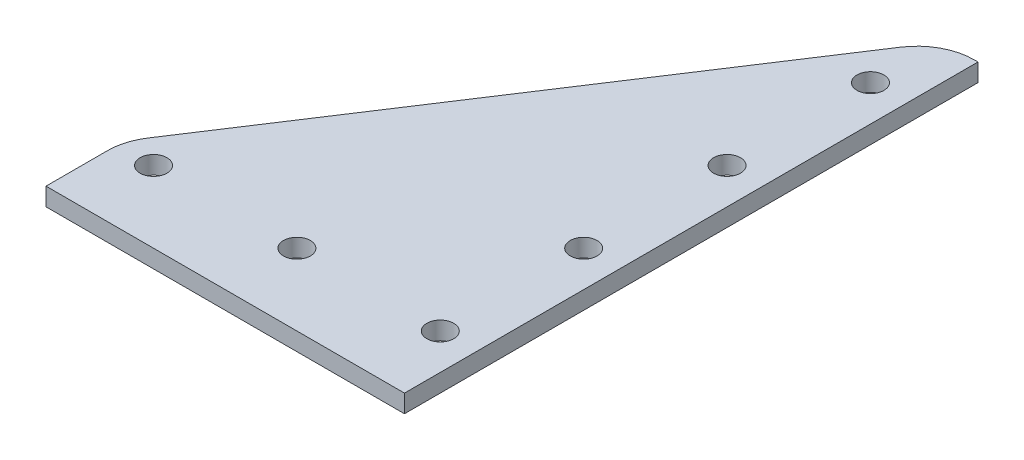
SolidWorks part; units mm, degrees
ref_plane "Front Plane" through (0, 0, 0) normal (0, 0, 1) x (1, 0, 0)
ref_plane "Top Plane" through (0, 0, 0) normal (0, 1, 0) x (1, 0, 0)
ref_plane "Right Plane" through (0, 0, 0) normal (1, 0, 0) x (0, 0, -1)
sketch "Sketch1" plane through (0, 0, 0) normal (0, 1, 0) x (1, 0, 0)
  line L1 (-31.75, 50.8) -> (31.75, 50.8)
  line L2 (-31.75, 50.8) -> (-31.75, -50.8)
  line L3 (-31.75, -50.8) -> (31.75, -50.8)
  line L4 (31.75, 50.8) -> (31.75, -50.8)
  line L5 (-31.75, 50.8) -> (31.75, -50.8) construction
  line L6 (-31.75, -50.8) -> (31.75, 50.8) construction
  point P0 (0, 0)
  dimension "D1" = 101.6
  dimension "D2" = 63.5
extrude "Boss-Extrude1" add sketch "Sketch1" along normal blind 3.175
sketch "Sketch2" plane through (0, 3.175, 0) normal (0, 1, 0) x (1, 0, 0)
  line L0 (-31.75, -50.8) -> (31.75, -50.8) construction
  line L1 (31.75, -50.8) -> (31.75, 50.8) construction
  circle A0 centre (25.4, -38.1) radius 2.3812
  circle A1 centre (25.4, -12.7) radius 2.3812
  circle A2 centre (25.4, 12.7) radius 2.3812
  circle A3 centre (25.4, 38.1) radius 2.3812
  circle A4 centre (0, -38.1) radius 2.3812
  circle A5 centre (-25.4, -38.1) radius 2.3812
  circle A6 centre (-50.8, -38.1) radius 2.3812
  dimension "D1" = 4.7625
  dimension "D2" = 12.7
  dimension "D3" = 6.35
  dimension "D4" = 4
  dimension "D5" = 4
extrude "Cut-Extrude1" cut sketch "Sketch2" against normal blind 3.175
sketch "Sketch3" plane through (0, 3.175, 0) normal (0, 1, 0) x (1, 0, 0)
  line L0 (-31.75, -36.9013) -> (25.6187, 50.8)
  line L1 (-31.75, 50.8) -> (-31.75, -50.8) construction
  line L2 (31.75, 50.8) -> (-31.75, 50.8) construction
  line L3 (25.6187, 50.8) -> (-31.75, 50.8)
  line L4 (-31.75, 50.8) -> (-31.75, -36.9013)
extrude "Cut-Extrude2" cut sketch "Sketch3" against normal through all
fillet "Fillet1" radius 10.16 2 edges at (-31.75, 1.5875, 36.9013) (25.6187, 1.5875, -50.8)
